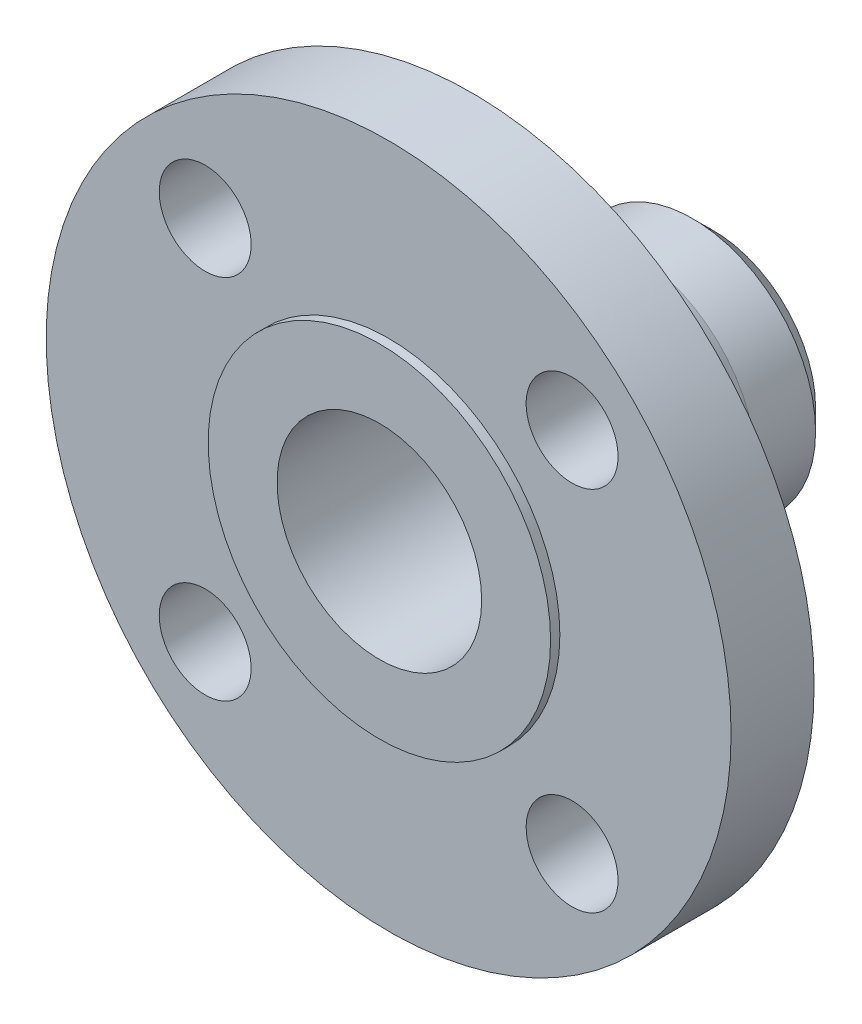
SolidWorks part; units mm, degrees
ref_plane "front" through (0, 0, 0) normal (0, 0, 1) x (1, 0, 0)
ref_plane "top" through (0, 0, 0) normal (0, 1, 0) x (1, 0, 0)
ref_plane "side" through (0, 0, 0) normal (1, 0, 0) x (0, 0, -1)
sketch "Hub Diameter" plane through (0, 0, 0) normal (0, 0, 1) x (1, 0, 0)
  circle A0 centre (0, 0) radius 29.337
ref_plane "Flange Start Plane" through (0, 0, -1.3801) normal (0, 0, 1) x (1, 0, 0)
ref_plane "Flange End Plane" through (0, 0, -14.224) normal (0, 0, 1) x (1, 0, 0)
extrude "Hub" add sketch "Hub Diameter" along normal blind 1.5875
sketch "Flange Diameter" plane through (0, 0, 0) normal (0, 0, 1) x (1, 0, 0)
  circle A0 centre (0, 0) radius 58.674
  dimension "Outside Diameter of Flange O" = 117.348
extrude "Flange" add sketch "Flange Diameter" against normal up to surface (14.224 mm away) up to plane "Flange End Plane"
ref_plane "Loft Start Plane" through (0, 0, -41.8253) normal (0, 0, 1) x (1, 0, 0)
sketch "hub dia at beginning of chamfer" plane through (0, 0, -14.224) normal (0, 0, -1) x (-1, 0, 0)
  circle A0 centre (0, 0) radius 29.337
sketch "Diameter of hub" plane through (0, 0, -41.8253) normal (0, 0, 1) x (1, 0, 0)
  circle A0 centre (0, 0) radius 21.082
ref_axis "Axis of pattern" through (0, 0, -50) along (0, 0, 1)
loft "Loft" add profiles "Diameter of hub", "hub dia at beginning of chamfer" connector at (-15.8138, 13.9418, -41.8253) connector at (-27.2085, 10.9708, -14.224)
ref_plane "Chamfer Start Plane" through (0, 0, -55.626) normal (0, 0, 1) x (1, 0, 0)
sketch "hub diameter at chamfer start" plane through (0, 0, -41.8253) normal (0, 0, -1) x (-1, 0, 0)
  circle A0 centre (0, 0) radius 21.082
extrude "Hub at chamfer" add sketch "hub diameter at chamfer start" along normal up to surface (13.8007 mm away) up to plane "Chamfer Start Plane"
chamfer "Chamfer" distance 3.556 angle 45 1 edges at (21.082, 0, -55.626)
sketch "Bore Diameter" plane through (0, 0, -55.626) normal (0, 0, 1) x (1, 0, 0)
  circle A0 centre (0, 0) radius 17.526
extrude "Bore" cut sketch "Bore Diameter" along normal up to next
sketch "Bolt Hole Diameter" plane through (0, 0, 0) normal (0, 0, 1) x (1, 0, 0)
  line L0 (0, 14.6053) -> (0, -13.3012) construction
  line L1 (-7.5167, -7.5167) -> (7.5167, 7.5167) construction
  circle A0 centre (31.4309, 31.4309) radius 7.874
  circle A1 centre (0, 0) radius 44.45 construction
  point P11 (0, 0)
  dimension "Diameter of Bolt Holes" = 15.748
  dimension "Diameter of Bolt Circle" = 88.9
  dimension "Angle" = 45
extrude "Bolt Hole" cut sketch "Bolt Hole Diameter" against normal through all
pattern_circular "Bolt Holes pattern" count 4 every 90 about axis through (0, 0, -50) along (0, 0, 1) of "Bolt Hole"
sketch "Sketch1" plane through (0, 0, 0) normal (0, 1, 0) x (1, 0, 0)
  line L1 (17.526, 55.626) -> (-17.526, 55.626) construction
  line L2 (-29.337, -1.5875) -> (29.337, -1.5875) construction
  point P0 (0, 55.626)
  point P1 (0, -1.5875)
other "CPoint1" parameters "Diameter"=31.75, "StubLength"=0
ref_axis "Axis1" through (0, 0, -65.626) along (0, 0, 1)
other "RPoint1"
ref_axis "Axis of Rotation" through (0, 0, -55.626) along (0, 0, 1)
ref_axis "Vertical" through (0, 0, -55.626) along (0, 1, 0)
equation "\"Flange Height@Flange Start Plane\" =  ( \"Hub Length for Welding Neck Y@Chamfer Start Plane\" - \"Thickness of Flange C@Flange End Plane\" )  / 30"
equation "\"Length of Hub at chamfer@Loft Start Plane\" =  ( 2 *  ( \"Hub Length for Welding Neck Y@Chamfer Start Plane\" - \"Thickness of Flange C@Flange End Plane\" )  )  / 3"
equation "\"Chamfer Length@Chamfer\"=(\"Hub diameter Beginning of Chamfer Welding Neck A@hub diameter at chamfer start\" -\"Bore Welding Neck B@Bore Diameter\")/2.0"
equation "\"Angular position of Bolt Holes@Bolt Holes pattern\" = 360/\"Number of Bolts@Bolt Holes pattern\""
